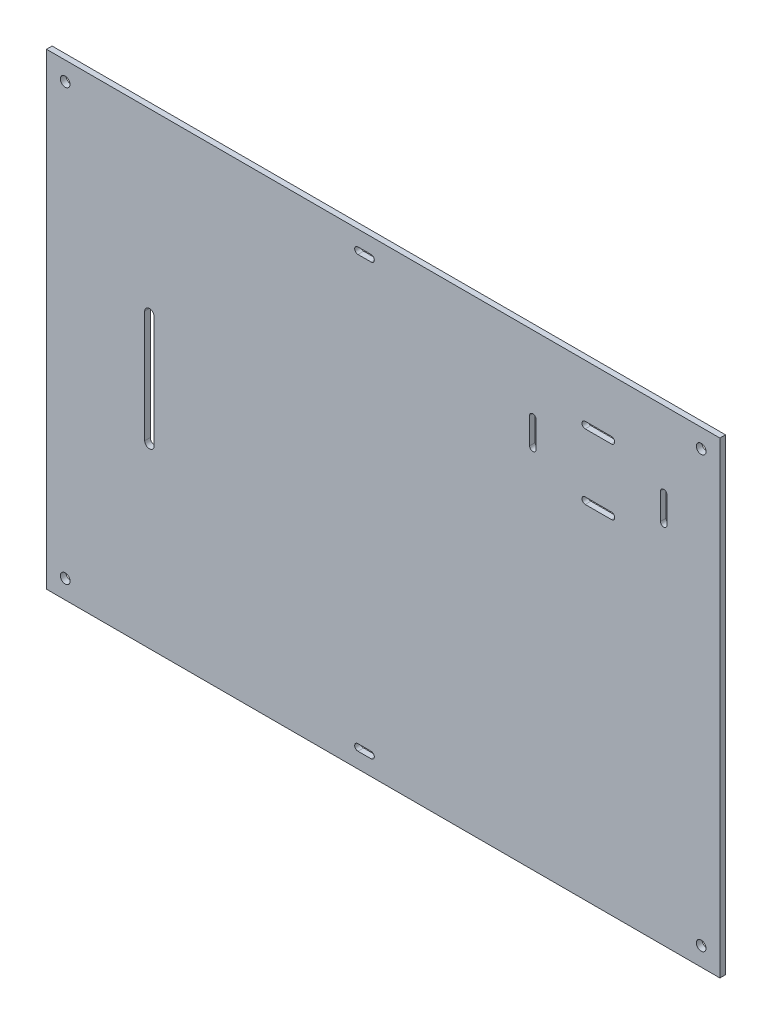
SolidWorks part; units mm, degrees
ref_plane "Front Plane" through (0, 0, 0) normal (0, 0, 1) x (1, 0, 0)
ref_plane "Top Plane" through (0, 0, 0) normal (0, 1, 0) x (1, 0, 0)
ref_plane "Right Plane" through (0, 0, 0) normal (1, 0, 0) x (0, 0, -1)
sketch "Sketch1" plane through (0, 0, 0) normal (0, 0, 1) x (1, 0, 0)
  line L0 (180, 125) -> (-180, -125) construction
  line L1 (-180, 125) -> (180, 125)
  line L2 (-180, 125) -> (-180, -125)
  line L3 (-180, -125) -> (180, -125)
  line L4 (180, 125) -> (180, -125)
  point P4 (0, 0)
  dimension "D1" = 360
  dimension "D2" = 250
base flange "Base-Flange1" sketch "Sketch1" thickness 3 reverse thickness direction no parameters "D1"=3
hole_wizard "#6 (0.204) Diameter Slot1" positions "Sketch7" profile "Sketch6" size "#6" standard "ANSI Inch" slot yes end condition through all
sketch "Sketch7" plane through (0, 0, 0) normal (0, 0, 1) x (1, 0, 0)
  line L0 (-180, 125) -> (-180, -125) construction
  line L1 (180, 125) -> (-180, 125) construction
  line L2 (180, -125) -> (180, 125) construction
  line L3 (-180, -125) -> (180, -125) construction
  point P0 (-170, -115)
  point P2 (-170, 115)
  point P4 (170, 115)
  point P6 (170, -115)
  dimension "D1" = 10
  dimension "D2" = 10
  dimension "D3" = 10
  dimension "D4" = 10
  dimension "D5" = 10
  dimension "D6" = 10
  dimension "D7" = 10
  dimension "D8" = 10
sketch "Sketch6" plane through (-170, -115, 0) normal (1, 0, 0) x (0, -1, 0)
  line L0 (0, 0) -> (0, 3)
  line L1 (0, 3) -> (2.5908, 3)
  line L2 (2.5908, 3) -> (2.5908, 0)
  line L5 (2.5908, 0) -> (0, 0)
  line L11 (0, -6.35) -> (0, 107.95) construction
  dimension "Thru Hole Dia." = 5.1816
  dimension "Thru Hole Depth" = 3
sketch "Sketch8" plane through (0, 0, 0) normal (0, 0, 1) x (1, 0, 0)
  line L0 (-13.5, -115) -> (-6.5, -115) construction
  line L1 (-13.5, -113.25) -> (-6.5, -113.25)
  line L2 (-13.5, -116.75) -> (-6.5, -116.75)
  line L3 (-180, -125) -> (180, -125) construction
  line L4 (-180, 125) -> (-180, -125) construction
  arc A0 (-13.5, -113.25) -> (-13.5, -116.75) centre (-13.5, -115) ccw
  arc A1 (-6.5, -116.75) -> (-6.5, -113.25) centre (-6.5, -115) ccw
  point P2 (-10, -115)
  dimension "D1" = 10
  dimension "D2" = 170
extrude "Cut-Extrude1" cut sketch "Sketch8" against normal blind 10
sketch "Sketch9" plane through (0, 0, 0) normal (0, 0, 1) x (1, 0, 0)
  line L0 (-13.5, 115) -> (-6.5, 115) construction
  line L1 (-13.5, 116.75) -> (-6.5, 116.75)
  line L2 (-13.5, 113.25) -> (-6.5, 113.25)
  line L3 (180, 125) -> (-180, 125) construction
  line L4 (-180, 125) -> (-180, -125) construction
  arc A0 (-13.5, 116.75) -> (-13.5, 113.25) centre (-13.5, 115) ccw
  arc A1 (-6.5, 113.25) -> (-6.5, 116.75) centre (-6.5, 115) ccw
  point P2 (-10, 115)
  dimension "D1" = 10
  dimension "D2" = 170
extrude "Cut-Extrude2" cut sketch "Sketch9" against normal blind 10
sketch "Sketch10" plane through (0, 0, 0) normal (0, 0, 1) x (1, 0, 0)
  line L0 (150, 84.5) -> (150, 70.5) construction
  line L1 (151.75, 84.5) -> (151.75, 70.5)
  line L2 (148.25, 84.5) -> (148.25, 70.5)
  line L3 (180, -125) -> (180, 125) construction
  line L4 (180, 125) -> (-180, 125) construction
  arc A0 (151.75, 84.5) -> (148.25, 84.5) centre (150, 84.5) ccw
  arc A1 (148.25, 70.5) -> (151.75, 70.5) centre (150, 70.5) ccw
  point P2 (150, 77.5)
  dimension "D1" = 30
  dimension "D2" = 47.5
extrude "Cut-Extrude4" cut sketch "Sketch10" against normal blind 10
sketch "Sketch11" plane through (0, 0, 0) normal (0, 0, 1) x (1, 0, 0)
  line L0 (108, 95) -> (122, 95) construction
  line L1 (108, 96.75) -> (122, 96.75)
  line L2 (108, 93.25) -> (122, 93.25)
  line L3 (180, 125) -> (-180, 125) construction
  line L4 (180, -125) -> (180, 125) construction
  arc A0 (108, 96.75) -> (108, 93.25) centre (108, 95) ccw
  arc A1 (122, 93.25) -> (122, 96.75) centre (122, 95) ccw
  point P2 (115, 95)
  dimension "D1" = 30
  dimension "D2" = 65
extrude "Cut-Extrude5" cut sketch "Sketch11" against normal blind 10
sketch "Sketch12" plane through (0, 0, 0) normal (0, 0, 1) x (1, 0, 0)
  line L0 (108, 60) -> (122, 60) construction
  line L1 (108, 61.75) -> (122, 61.75)
  line L2 (108, 58.25) -> (122, 58.25)
  line L3 (180, -125) -> (180, 125) construction
  line L4 (180, 125) -> (-180, 125) construction
  arc A0 (108, 61.75) -> (108, 58.25) centre (108, 60) ccw
  arc A1 (122, 58.25) -> (122, 61.75) centre (122, 60) ccw
  point P2 (115, 60)
  dimension "D1" = 65
  dimension "D2" = 65
extrude "Cut-Extrude6" cut sketch "Sketch12" against normal blind 10
sketch "Sketch13" plane through (0, 0, 0) normal (0, 0, 1) x (1, 0, 0)
  line L0 (80, 84.5) -> (80, 70.5) construction
  line L1 (81.75, 84.5) -> (81.75, 70.5)
  line L2 (78.25, 84.5) -> (78.25, 70.5)
  line L3 (180, -125) -> (180, 125) construction
  line L4 (180, 125) -> (-180, 125) construction
  arc A0 (81.75, 84.5) -> (78.25, 84.5) centre (80, 84.5) ccw
  arc A1 (78.25, 70.5) -> (81.75, 70.5) centre (80, 70.5) ccw
  point P2 (80, 77.5)
  dimension "D1" = 100
  dimension "D2" = 47.5
extrude "Cut-Extrude7" cut sketch "Sketch13" against normal blind 10
sketch "Sketch14" plane through (0, 0, 0) normal (0, 0, 1) x (1, 0, 0)
  line L0 (-125, 30) -> (-125, -30) construction
  line L1 (-122.5, 30) -> (-122.5, -30)
  line L2 (-127.5, 30) -> (-127.5, -30)
  line L3 (-180, 125) -> (-180, -125) construction
  line L4 (180, 125) -> (-180, 125) construction
  arc A0 (-122.5, 30) -> (-127.5, 30) centre (-125, 30) ccw
  arc A1 (-127.5, -30) -> (-122.5, -30) centre (-125, -30) ccw
  point P2 (-125, 0)
  dimension "D1" = 55
  dimension "D2" = 125
extrude "Cut-Extrude8" cut sketch "Sketch14" against normal blind 10
sketch "Bend-Lines1" plane through (0, 0, 0) normal (0, 1, 0) x (1, 0, 0)
sketch "Bounding-Box1" plane through (0, 0, 0) normal (0, 1, 0) x (1, 0, 0)
sheet metal parameters "Sheet-Metal1" thickness 3 parameters "D1"=3
flat pattern "Flat-Pattern1" [suppressed]
sketch "Bend-Lines2" plane through (0, 0, 0) normal (0, 1, 0) x (1, 0, 0)
sketch "Bounding-Box2" [suppressed] plane through (0, 0, 0) normal (0, 1, 0) x (1, 0, 0)
sheet metal parameters "Sheet-Metal2" thickness 3 parameters "D1"=3
flat pattern "Flat-Pattern1"
sketch "Bend-Lines2" plane through (0, 0, 0) normal (0, 1, 0) x (1, 0, 0)
sketch "Bounding-Box2" [suppressed] plane through (0, 0, 0) normal (0, 1, 0) x (1, 0, 0)
sheet metal parameters "Sheet-Metal3" thickness 3 parameters "D1"=3
flat pattern "Flat-Pattern1"
sketch "Bend-Lines2" plane through (0, 0, 0) normal (0, 1, 0) x (1, 0, 0)
sketch "Bounding-Box2" [suppressed] plane through (0, 0, 0) normal (0, 1, 0) x (1, 0, 0)
sheet metal parameters "Sheet-Metal4" thickness 3 parameters "D1"=3
flat pattern "Flat-Pattern1"
sketch "Bend-Lines2" plane through (0, 0, 0) normal (0, 1, 0) x (1, 0, 0)
sketch "Bounding-Box2" [suppressed] plane through (0, 0, 0) normal (0, 1, 0) x (1, 0, 0)
sheet metal parameters "Sheet-Metal6" thickness 3 parameters "D1"=3
flat pattern "Flat-Pattern1"
sketch "Bend-Lines2" plane through (0, 0, 0) normal (0, 1, 0) x (1, 0, 0)
sketch "Bounding-Box2" [suppressed] plane through (0, 0, 0) normal (0, 1, 0) x (1, 0, 0)
sheet metal parameters "Sheet-Metal7" thickness 3 parameters "D1"=3
flat pattern "Flat-Pattern1"
sketch "Bend-Lines2" plane through (0, 0, 0) normal (0, 1, 0) x (1, 0, 0)
sketch "Bounding-Box2" [suppressed] plane through (0, 0, 0) normal (0, 1, 0) x (1, 0, 0)
sheet metal parameters "Sheet-Metal8" thickness 3 parameters "D1"=3
flat pattern "Flat-Pattern1"
sketch "Bend-Lines2" plane through (0, 0, 0) normal (0, 1, 0) x (1, 0, 0)
sketch "Bounding-Box2" [suppressed] plane through (0, 0, 0) normal (0, 1, 0) x (1, 0, 0)
sheet metal parameters "Sheet-Metal9" thickness 3 parameters "D1"=3
flat pattern "Flat-Pattern1"
sketch "Bend-Lines2" plane through (0, 0, 0) normal (0, 1, 0) x (1, 0, 0)
sketch "Bounding-Box2" [suppressed] plane through (0, 0, 0) normal (0, 1, 0) x (1, 0, 0)
sheet metal parameters "Sheet-Metal10" thickness 3 parameters "D1"=3
flat pattern "Flat-Pattern1"
sketch "Bend-Lines2" plane through (0, 0, 0) normal (0, 1, 0) x (1, 0, 0)
sketch "Bounding-Box2" [suppressed] plane through (0, 0, 0) normal (0, 1, 0) x (1, 0, 0)
